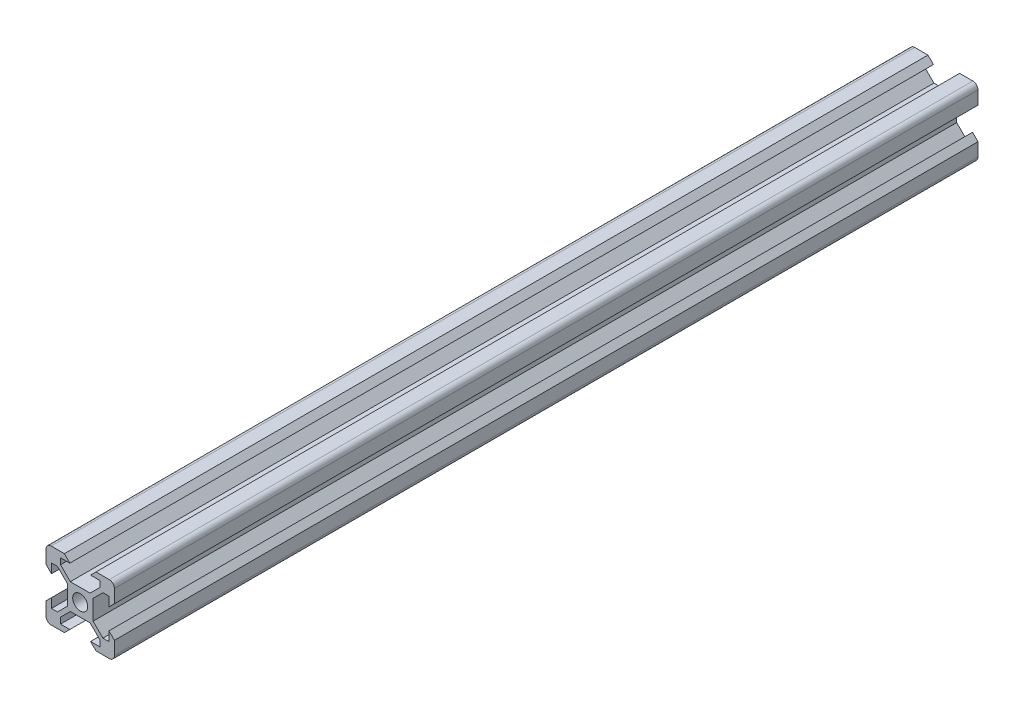
SolidWorks part; units mm, degrees
ref_plane "Front Plane" through (0, 0, 0) normal (0, 0, 1) x (1, 0, 0)
ref_plane "Top Plane" through (0, 0, 0) normal (0, 1, 0) x (1, 0, 0)
ref_plane "Right Plane" through (0, 0, 0) normal (1, 0, 0) x (0, 0, -1)
sketch "Sketch1" plane through (0, 0, 0) normal (0, 0, 1) x (1, 0, 0)
  line L0 (-5.7847, 7.544) -> (-11.512, 13.2713)
  line L1 (-7.544, 7.544) -> (7.544, 7.544)
  line L2 (-7.544, 7.544) -> (-7.544, -7.544)
  line L3 (-7.544, -7.544) -> (7.544, -7.544)
  line L4 (7.544, 7.544) -> (7.544, -7.544)
  line L5 (-7.544, 7.544) -> (7.544, -7.544) construction
  line L6 (-7.544, -7.544) -> (7.544, 7.544) construction
  line L7 (-11.512, 13.2713) -> (-11.512, 16.8)
  line L8 (-11.512, 16.8) -> (-6.052, 16.8)
  line L9 (-6.052, 16.8) -> (-9.252, 20)
  line L10 (-9.252, 20) -> (-17, 20)
  line L11 (-20, 17) -> (-20, 9.252)
  line L12 (-20, 9.252) -> (-16.8, 6.052)
  line L13 (-16.8, 6.052) -> (-16.8, 11.512)
  line L14 (-16.8, 11.512) -> (-13.2713, 11.512)
  line L15 (-13.2713, 11.512) -> (-7.544, 5.7847)
  line L16 (-19.1213, 19.1213) -> (0, 0) construction
  line L17 (13.2713, 11.512) -> (16.8, 11.512)
  line L18 (20, 9.252) -> (20, 17)
  line L19 (17, 20) -> (9.252, 20)
  line L20 (9.252, 20) -> (6.052, 16.8)
  line L21 (6.052, 16.8) -> (11.512, 16.8)
  line L22 (11.512, 16.8) -> (11.512, 13.2713)
  line L23 (11.512, 13.2713) -> (5.7847, 7.544)
  line L24 (7.544, 5.7847) -> (13.2713, 11.512)
  line L25 (16.8, 11.512) -> (16.8, 6.052)
  line L26 (16.8, 6.052) -> (20, 9.252)
  line L27 (19.1213, 19.1213) -> (0, 0) construction
  line L28 (11.512, -13.2713) -> (11.512, -16.8)
  line L29 (9.252, -20) -> (17, -20)
  line L30 (20, -17) -> (20, -9.252)
  line L31 (20, -9.252) -> (16.8, -6.052)
  line L32 (16.8, -6.052) -> (16.8, -11.512)
  line L33 (16.8, -11.512) -> (13.2713, -11.512)
  line L34 (13.2713, -11.512) -> (7.544, -5.7847)
  line L35 (5.7847, -7.544) -> (11.512, -13.2713)
  line L36 (11.512, -16.8) -> (6.052, -16.8)
  line L37 (6.052, -16.8) -> (9.252, -20)
  line L38 (19.1213, -19.1213) -> (0, 0) construction
  line L39 (-13.2713, -11.512) -> (-16.8, -11.512)
  line L40 (-20, -9.252) -> (-20, -17)
  line L41 (-17, -20) -> (-9.252, -20)
  line L42 (-9.252, -20) -> (-6.052, -16.8)
  line L43 (-6.052, -16.8) -> (-11.512, -16.8)
  line L44 (-11.512, -16.8) -> (-11.512, -13.2713)
  line L45 (-11.512, -13.2713) -> (-5.7847, -7.544)
  line L46 (-7.544, -5.7847) -> (-13.2713, -11.512)
  line L47 (-16.8, -11.512) -> (-16.8, -6.052)
  line L48 (-16.8, -6.052) -> (-20, -9.252)
  line L49 (-19.1213, -19.1213) -> (0, 0) construction
  circle A0 centre (0, 0) radius 4.4
  arc A1 (-17, 20) -> (-20, 17) centre (-17, 17) ccw
  arc A2 (20, 17) -> (17, 20) centre (17, 17) ccw
  arc A3 (17, -20) -> (20, -17) centre (17, -17) ccw
  arc A4 (-20, -17) -> (-17, -20) centre (-17, -17) ccw
  point P66 (0, 0)
  dimension "D1" = 8.8
  dimension "D8" = 3
  dimension "D2" = 15.088
  dimension "D3" = 2.488
  dimension "D4" = 8.488
  dimension "D5" = 3.2
  dimension "D6" = 20
  dimension "D7" = 15.2
  dimension "D9" = 4
extrude "Boss-Extrude1" add sketch "Sketch1" along normal mid plane 505 contours L10 A1 L11 L12 L13 L14 L15 L2 L1 L0 L7 L8 L9 | L18 A2 L19 L20 L21 L22 L23 L1 L4 L24 L17 L25 L26 | L40 A4 L41 L42 L43 L44 L45 L3 L2 L46 L39 L47 L48 | L29 A3 L30 L31 L32 L33 L34 L4 L3 L35 L28 L36 L37 | L4 L1 L2 L3 A0 region at (-14.3184, 14.3184, 0) region at (0, 7.3306, 0) region at (14.3184, 14.3184, 0) region at (-14.3184, -14.3184, 0) region at (14.3184, -14.3184, 0)
equation "\"longitud\"= 800"
